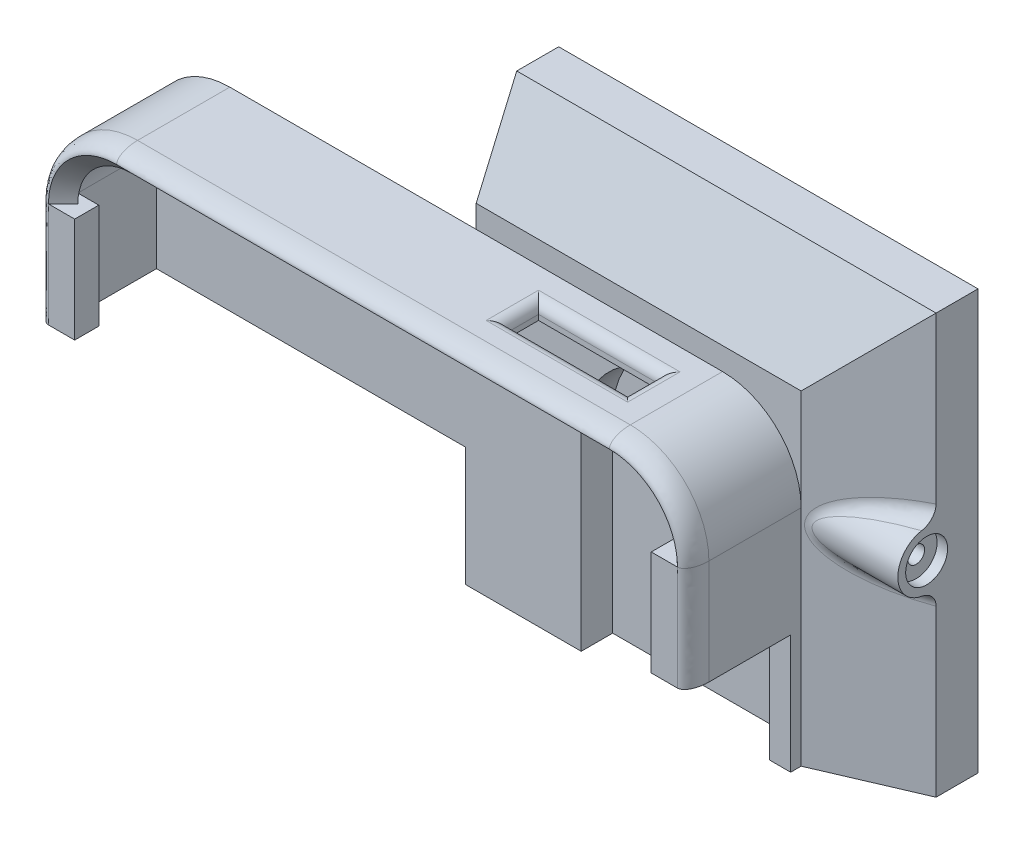
SolidWorks part; units mm, degrees
ref_plane "Front Plane" through (0, 0, 0) normal (0, 0, 1) x (1, 0, 0)
ref_plane "Top Plane" through (0, 0, 0) normal (0, 1, 0) x (1, 0, 0)
ref_plane "Right Plane" through (0, 0, 0) normal (1, 0, 0) x (0, 0, -1)
sketch "Sketch1" plane through (0, 0, 0) normal (0, 0, 1) x (1, 0, 0)
  line L0 (31, 17.5) -> (31, 0)
  line L1 (0, 0) -> (62, 0)
  line L2 (0, 0) -> (0, 10)
  line L3 (7.5, 17.5) -> (54.5, 17.5)
  line L4 (62, 0) -> (62, 10)
  line L5 (7.5, 16) -> (54.5, 16)
  line L9 (1.5, 0) -> (1.5, 10)
  line L12 (60.5, 10) -> (60.5, 0)
  arc A0 (0, 10) -> (7.5, 17.5) centre (7.5, 10) cw
  arc A1 (62, 10) -> (54.5, 17.5) centre (54.5, 10) ccw
  arc A2 (1.5, 10) -> (7.5, 16) centre (7.5, 10) cw
  arc A3 (60.5, 10) -> (54.5, 16) centre (54.5, 10) ccw
  dimension "D5" = 1.5
extrude "Boss-Extrude1" add sketch "Sketch1" along normal blind 10.8 contours L9 A2 L5 L0 L3 A0 L2 L1 | A3 L12 L1 L4 A1 L3 L0 L5 region at (42.75, 17.144, 0) region at (30.644, 16.75, 0)
sketch "Sketch2" plane through (0, 0, 0) normal (0, 0, -1) x (-1, 0, 0)
  line L0 (-1.5, 0) -> (-1.5, 10)
  line L1 (-7.5, 16) -> (-54.5, 16)
  line L2 (-60.5, 0) -> (-60.5, 10)
  line L3 (-60.5, 0) -> (-1.5, 0)
  arc A0 (-1.5, 10) -> (-7.5, 16) centre (-7.5, 10) ccw
  arc A1 (-54.5, 16) -> (-60.5, 10) centre (-54.5, 10) ccw
extrude "Boss-Extrude2" add sketch "Sketch2" against normal blind 1 separate body
combine bodies "Combine1" operation type add bodies to combine 102 101
sketch "Sketch3" plane through (0, 0, 10.8) normal (0, 0, 1) x (1, 0, 0)
  line L0 (0, 0) -> (3.5, 0)
  line L1 (0, 0) -> (0, 10)
  line L2 (0, 0) -> (0, 10) construction
  line L3 (3.5, 0) -> (3.5, 10)
  line L4 (3.5, 10) -> (0, 10)
  line L5 (1.5, 10) -> (1.5, 0)
  line L6 (31, 16) -> (31, -7.5027)
  line L7 (7.5, 16) -> (54.5, 16) construction
  line L8 (60.5, 10) -> (60.5, 0)
  line L9 (62, 0) -> (58.5, 0)
  line L10 (58.5, 10) -> (62, 10)
  line L11 (58.5, 0) -> (58.5, 10)
  line M7 (1.5, 0) -> (1.5, 10)
  line M11 (60.5, 10) -> (60.5, 0)
  dimension "D1" = 3.5
  dimension "D2" = 10
extrude "Boss-Extrude3" add sketch "Sketch3" against normal blind 2.3 contours L3 L4 L0 M7 | L11 L9 L10 M11 region at (2.5, 5, 10.8) region at (59.5, 5, 10.8)
fillet "Fillet1" radius 1 5 edges at (0, 5, 10.8) (62, 5, 10.8) (2.1967, 15.3033, 10.8) (59.8033, 15.3033, 10.8) (31, 17.5, 10.8) second distance 2 first distance on face at (31, 9.4708, 10.8)
sketch "Sketch4" plane through (0, 17.5, 0) normal (0, 1, 0) x (1, 0, 0)
  line L0 (62, -8.8) -> (62, 0) construction
  line L1 (51.5, -6.05) -> (40, -6.05)
  line L2 (51.5, -6.05) -> (51.5, -3.05)
  line L3 (51.5, -3.05) -> (40, -3.05)
  line L4 (40, -6.05) -> (40, -3.05)
  line L5 (7.5, 0) -> (54.5, 0) construction
  dimension "D1" = 10.5
  dimension "D2" = 11.5
  dimension "D3" = 3.05
  dimension "D4" = 3
extrude "Cut-Extrude1" cut sketch "Sketch4" against normal up to next
sketch "Sketch5" plane through (0, 0, 10.8) normal (0, 0, 1) x (1, 0, 0)
  line L1 (7.5, 15) -> (54.5, 15)
  line L2 (7.5, 16) -> (54.5, 16) construction
  line L4 (3.5, 10) -> (1.5, 10) construction
  line L5 (31, 16.5) -> (31, -2.3238) construction
  line L6 (54.5, 16.5) -> (7.5, 16.5) construction
  line L7 (59.5, 10) -> (60.5, 10)
  line L8 (54.5, 16) -> (7.5, 16)
  line L9 (1.5, 10) -> (2.5, 10)
  arc A1 (2.5, 10) -> (7.5, 15) centre (7.5, 10) cw
  arc A2 (59.5, 10) -> (54.5, 15) centre (54.5, 10) ccw
  arc A3 (60.5, 10) -> (54.5, 16) centre (54.5, 10) ccw
  arc A4 (7.5, 16) -> (1.5, 10) centre (7.5, 10) ccw
  dimension "D1" = 1
extrude "Boss-Extrude4" add sketch "Sketch5" against normal blind 2.3
chamfer "Chamfer1" distance 1.5 angle 45 3 edges at (58.0355, 13.5355, 10.8) (31, 15, 10.8) (3.9645, 13.5355, 10.8)
chamfer "Chamfer3" distance 1 angle 45 3 edges at (58.0355, 13.5355, 8.5) (31, 15, 8.5) (3.9645, 13.5355, 8.5)
sketch "Sketch6" plane through (0, 0, 0) normal (0, 0, -1) x (-1, 0, 0)
  line L0 (-59.98, 0) -> (-59.98, 6.7)
  line L1 (-59.98, 0) -> (-42.02, 0)
  line L2 (-42.02, 0) -> (-42.02, 6.7)
  arc A0 (-42.02, 6.7) -> (-59.98, 6.7) centre (-51, 6.7) ccw
extrude "Cut-Extrude2" cut sketch "Sketch6" against normal blind 2
sketch "Sketch9" plane through (0, 0, 0) normal (0, 0, -1) x (-1, 0, 0)
  line L0 (-62, 10) -> (-62, 0)
  line L1 (-62, 0) -> (-59.98, 0)
  line L2 (-59.98, 0) -> (-59.98, 6.7)
  line L3 (-42.02, 6.7) -> (-42.02, 0)
  line L4 (-42.02, 0) -> (-40, 0)
  line L5 (-42.02, 0) -> (0, 0) construction
  line L6 (-40, 0) -> (-40, 10)
  line L8 (-54.5, 17.5) -> (-47.5, 17.5)
  arc A0 (-59.98, 6.7) -> (-42.02, 6.7) centre (-51, 6.7) cw
  arc A1 (-47.5, 17.5) -> (-40, 10) centre (-47.5, 10) cw
  arc A2 (-54.5, 17.5) -> (-62, 10) centre (-54.5, 10) ccw
extrude "Boss-Extrude6" add sketch "Sketch9" along normal blind 2
fillet "Fillet2" radius 1 4 edges at (45.75, 17.5, 3.05) (51.5, 17.5, 4.55) (45.75, 17.5, 6.05) (40, 17.5, 4.55)
sketch "Sketch10" plane through (0, 0, -2) normal (0, 0, -1) x (-1, 0, 0)
  line L0 (-62, 10) -> (-62, 0)
  line L1 (-62, 0) -> (-40, 0)
  line L2 (-40, 0) -> (-40, 10)
  line L3 (-54.5, 17.5) -> (-47.5, 17.5)
  arc A0 (-62, 10) -> (-54.5, 17.5) centre (-54.5, 10) cw
  arc A1 (-40, 10) -> (-47.5, 17.5) centre (-47.5, 10) ccw
extrude "Boss-Extrude7" add sketch "Sketch10" along normal blind 1.87
sketch "Sketch11" plane through (0, 0, -2) normal (0, 0, 1) x (1, 0, 0)
  circle A0 centre (51, 8.65) radius 2.5
  dimension "D1" = 5
extrude "Cut-Extrude3" cut sketch "Sketch11" against normal through all
sketch "Sketch20" plane through (0, 0, -3.87) normal (0, 0, -1) x (-1, 0, 0)
  line L0 (-51, 28.65) -> (-51, -11.35) construction
  line L1 (-71, 28.65) -> (-31, 28.65)
  line L2 (-71, 28.65) -> (-71, -11.35)
  line L3 (-71, -11.35) -> (-31, -11.35)
  line L4 (-31, 28.65) -> (-31, -11.35)
  line L5 (-71, 8.65) -> (-31, 8.65) construction
  line L7 (-68.6, 26.25) -> (-33.4, 26.25)
  line L8 (-68.6, 26.25) -> (-68.6, -8.95)
  line L9 (-68.6, -8.95) -> (-33.4, -8.95)
  line L10 (-33.4, 26.25) -> (-33.4, -8.95)
  circle A0 centre (-51, 8.65) radius 2.5 construction
  dimension "D1" = 40
  dimension "D2" = 40
  dimension "D3" = 0
  dimension "D4" = 0
  dimension "D5" = 35.2
  dimension "D6" = 35.2
  dimension "D7" = 17.6
  dimension "D8" = 17.6
extrude "Boss-Extrude8" add sketch "Sketch20" along normal blind 4 separate body
sketch "Sketch21" plane through (0, 0, 0) normal (0, -1, 0) x (1, 0, 0)
  line L0 (62, -3.87) -> (71, -3.87)
  line L1 (71, -3.87) -> (62, 0)
  line L2 (62, 8.8) -> (62, -3.87) construction
  line L3 (62, 0) -> (62, -3.87)
  dimension "D1" = 9
extrude "Boss-Extrude9" add sketch "Sketch21" along normal up to surface and the other way up to surface up to face at (51, -11.35, -5.87) other way up to face at (51, 28.65, -5.87)
sketch "Sketch28" plane through (0, 0, 0) normal (0, 0, -1) x (-1, 0, 0)
  line L0 (-31, 17.5) -> (-31, 0)
  line L1 (-31, -11.35) -> (-31, 28.65) construction
  line L4 (-40, 10) -> (-40, 0)
  line L5 (-40, 0) -> (0, 0)
  line L6 (0, 0) -> (0, 10)
  line L7 (-7.5, 17.5) -> (-47.5, 17.5)
  line L8 (-40, 10) -> (-40, 0)
  line L9 (-40, 0) -> (0, 0)
  line L10 (0, 0) -> (0, 10)
  line L11 (-7.5, 17.5) -> (-47.5, 17.5)
  arc A2 (-40, 10) -> (-47.5, 17.5) centre (-47.5, 10) ccw
  arc A3 (0, 10) -> (-7.5, 17.5) centre (-7.5, 10) ccw
  arc A4 (-40, 10) -> (-47.5, 17.5) centre (-47.5, 10) ccw
  arc A5 (0, 10) -> (-7.5, 17.5) centre (-7.5, 10) ccw
  arc M7 (-47.5, 17.5) -> (-40, 10) centre (-47.5, 10) cw
  line M8 (-40, 10) -> (-40, 0)
  line M9 (-40, 0) -> (0, 0)
  line M12 (-7.5, 17.5) -> (-47.5, 17.5)
  dimension "D1" = 0
extrude "Boss-Extrude22" add sketch "Sketch28" along normal up to surface (3.87 mm away) contours L0 M12 M7 M8 M9 region at (35.9396, 9.2536, 0) up to face at (53.5, 8.65, -3.87)
sketch "Sketch29" plane through (31, 0, 0) normal (-1, 0, 0) x (0, 0, 1)
  line L0 (-3.87, 28.65) -> (-3.87, 19.65)
  line L1 (-3.87, 17.5) -> (-3.87, 28.65) construction
  line L2 (-3.87, 19.65) -> (0, 19.65)
  line L3 (0, 19.65) -> (-3.87, 28.65)
  line L4 (-3.87, 28.65) -> (-3.8304, 28.713)
  line M6 (-3.87, 17.5) -> (-3.87, 28.65)
  dimension "D1" = 9
extrude "Boss-Extrude23" add sketch "Sketch29" against normal up to surface (40 mm away) contours L2 L3 M6 region at (31, 22.65, -2.58) up to face at (71, 8.65, -5.87)
sketch "Sketch30" plane through (0, 19.65, 0) normal (0, -1, 0) x (1, 0, 0)
  line L3 (62, 0) -> (71, -3.87)
  line L4 (71, -3.87) -> (71, 0)
  line L5 (71, 0) -> (62, 0)
  line L6 (62, 0) -> (71, -3.87)
  line L7 (71, -3.87) -> (71, 0)
  line L8 (71, 0) -> (62, 0)
  dimension "D1" = 0
extrude "Cut-Extrude8" cut sketch "Sketch30" against normal up to next
sketch "Sketch31" plane through (62, 0, 0) normal (-1, 0, 0) x (0, 0, 1)
  line L3 (0, 28.65) -> (-3.87, 28.65)
  line L4 (-3.87, 28.65) -> (0, 19.65)
  line L5 (0, 19.65) -> (0, 28.65)
  line L6 (0, 28.65) -> (-3.87, 28.65)
  line L7 (-3.87, 28.65) -> (0, 19.65)
  line L8 (0, 19.65) -> (0, 28.65)
  dimension "D1" = 0
extrude "Cut-Extrude9" cut sketch "Sketch31" against normal up to next
sketch "Sketch32" plane through (0, 19.65, 0) normal (0, -1, 0) x (1, 0, 0)
  line L5 (62, -3.87) -> (62, 0)
  line L6 (62, 0) -> (31, 0)
  line L7 (31, 0) -> (31, -3.87)
  line L8 (31, -3.87) -> (33.4, -3.87)
  line L9 (33.4, -3.87) -> (62, -3.87)
  line L10 (62, -3.87) -> (62, 0)
  line L11 (62, 0) -> (31, 0)
  line L12 (31, 0) -> (31, -3.87)
  line L13 (31, -3.87) -> (33.4, -3.87)
  line L14 (33.4, -3.87) -> (62, -3.87)
  dimension "D1" = 0
extrude "Boss-Extrude24" add sketch "Sketch32" along normal up to surface (2.15 mm away) up to face at (45.75, 17.5, 4.55)
sketch "Sketch33" plane through (0, 0, -3.87) normal (0, 0, -1) x (-1, 0, 0)
  line L0 (-54.5, 17.5) -> (-62, 17.5)
  line L1 (-62, 17.5) -> (-62, 10)
  arc A0 (-62, 10) -> (-54.5, 17.5) centre (-54.5, 10) cw
extrude "Boss-Extrude25" add sketch "Sketch33" against normal up to surface (3.87 mm away) up to face at (48.1, 18.36, 0)
sketch "Sketch34" plane through (0, 0, 0) normal (0, -1, 0) x (1, 0, 0)
  line L0 (60.5, 1) -> (62, 1)
  line L1 (31, 0) -> (31, 1)
  line L20 (0, 0) -> (31, 0)
  line L21 (31, 0) -> (31, -3.87)
  line L22 (31, -3.87) -> (33.4, -3.87)
  line L23 (33.4, -3.87) -> (62, -3.87)
  line L24 (62, -3.87) -> (62, 0)
  line L25 (62, 0) -> (62, 8.8)
  line L26 (61, 10.8) -> (58.5, 10.8)
  line L27 (58.5, 10.8) -> (58.5, 8.5)
  line L28 (58.5, 8.5) -> (60.5, 8.5)
  line L29 (60.5, 8.5) -> (60.5, 1)
  line L30 (60.5, 1) -> (59.98, 1)
  line L31 (59.98, 1) -> (59.98, -2)
  line L32 (59.98, -2) -> (42.02, -2)
  line L33 (42.02, -2) -> (42.02, 1)
  line L34 (42.02, 1) -> (1.5, 1)
  line L35 (1.5, 1) -> (1.5, 8.5)
  line L36 (1.5, 8.5) -> (3.5, 8.5)
  line L37 (3.5, 8.5) -> (3.5, 10.8)
  line L38 (3.5, 10.8) -> (1, 10.8)
  line L39 (0, 8.8) -> (0, 0)
  line L40 (0, 0) -> (31, 0)
  line L41 (31, 0) -> (31, -3.87)
  line L42 (31, -3.87) -> (33.4, -3.87)
  line L43 (33.4, -3.87) -> (62, -3.87)
  line L44 (62, -3.87) -> (62, 0)
  line L45 (62, 0) -> (62, 8.8)
  line L46 (61, 10.8) -> (58.5, 10.8)
  line L47 (58.5, 10.8) -> (58.5, 8.5)
  line L48 (58.5, 8.5) -> (60.5, 8.5)
  line L49 (60.5, 8.5) -> (60.5, 1)
  line L50 (60.5, 1) -> (59.98, 1)
  line L51 (59.98, 1) -> (59.98, -2)
  line L52 (59.98, -2) -> (42.02, -2)
  line L53 (42.02, -2) -> (42.02, 1)
  line L54 (42.02, 1) -> (1.5, 1)
  line L55 (1.5, 1) -> (1.5, 8.5)
  line L56 (1.5, 8.5) -> (3.5, 8.5)
  line L57 (3.5, 8.5) -> (3.5, 10.8)
  line L58 (3.5, 10.8) -> (1, 10.8)
  line L59 (0, 8.8) -> (0, 0)
  spline S2 degree 2 poles (-3722.018, -1283.947) (75.1864, -74.9368) (61.954, 9.3993) (61.9047, 9.714) (61.807, 9.9811) (61.6887, 10.3047) (61.5165, 10.5125) (61.4097, 10.6416) (61.2894, 10.7144) (30.6702, 29.2588) (-318.8135, -3970.7049) knots -71.74099 -71.74099 -71.74099 0.25 0.25 0.5 0.5 0.75 0.75 0.875 0.875 27.96208 27.96208 27.96208 only from (62, 8.8) to (61, 10.8)
  spline S3 degree 2 poles (335.3153, -3974.9417) (31.4549, 29.2365) (0.7111, 10.7147) (0.592, 10.643) (0.4846, 10.5139) (0.3135, 10.3082) (0.1946, 9.9856) (0.0962, 9.7183) (0.0462, 9.4006) (-13.1634, -74.4343) (3754.3791, -1367.695) knots -27.023504 -27.023504 -27.023504 0.125 0.125 0.25 0.25 0.5 0.5 0.75 0.75 72.303108 72.303108 72.303108 only from (1, 10.8) to (0, 8.8)
  spline S4 degree 2 poles (62, 8.8) (62, 9.1064) (61.954, 9.3993) (61.9047, 9.714) (61.807, 9.9811) (61.6887, 10.3047) (61.5165, 10.5125) (61.4097, 10.6416) (61.2894, 10.7144) (61.1481, 10.8) (61, 10.8) knots 0 0 0 0.25 0.25 0.5 0.5 0.75 0.75 0.875 0.875 1 1 1
  spline S5 degree 2 poles (1, 10.8) (0.8527, 10.8) (0.7111, 10.7147) (0.592, 10.643) (0.4846, 10.5139) (0.3135, 10.3082) (0.1946, 9.9856) (0.0962, 9.7183) (0.0462, 9.4006) (0, 9.1077) (0, 8.8) knots 0 0 0 0.125 0.125 0.25 0.25 0.5 0.5 0.75 0.75 1 1 1
  line M24 (31, 0) -> (31, -3.87)
  line M25 (31, -3.87) -> (33.4, -3.87)
  line M26 (33.4, -3.87) -> (62, -3.87)
  line M27 (62, -3.87) -> (62, 0)
  line M28 (62, 0) -> (62, 8.8)
  line M34 (60.5, 1) -> (59.98, 1)
  line M35 (59.98, 1) -> (59.98, -2)
  line M36 (59.98, -2) -> (42.02, -2)
  line M37 (42.02, -2) -> (42.02, 1)
  line M38 (42.02, 1) -> (1.5, 1)
  dimension "D1" = 0
extrude "Boss-Extrude26" add sketch "Sketch34" along normal up to surface (11.35 mm away) contours L1 L0 M24 M25 M26 M27 M28 M34 M35 M36 M37 M38 region at (58.1075, 0, -2.3535) region at (39.3369, 0, -1.8217) up to face at (57.25, -11.35, -4.8808)
sketch "Sketch37" plane through (71, 0, 0) normal (1, 0, 0) x (0, 0, -1)
  line L1 (3.87, -11.35) -> (3.87, 28.65) construction
  circle A0 centre (2.97, 8.65) radius 0.8065
  dimension "D2" = 1.613
  dimension "D3" = 0.9
  dimension "D1" = 17.6
extrude "Cut-Extrude13" cut sketch "Sketch37" against normal up to surface (17.5 mm away) up to face at (53.5, 8.65, -2)
sketch "Sketch38" plane through (71, 0, 0) normal (1, 0, 0) x (0, 0, -1)
  line L0 (3.87, 11.2486) -> (3.87, 6.0514)
  line L1 (3.87, -11.35) -> (3.87, 28.65) construction
  circle A0 centre (2.97, 8.65) radius 2.75
  line M3 (3.87, 28.65) -> (3.87, -11.35)
  dimension "D1" = 5.5
extrude "Boss-Extrude27" add sketch "Sketch38" against normal up to surface (9 mm away) contours A0 M3 region at (71, 8.65, -2.2712) up to face at (62, 0.3833, 4.65)
sketch "Sketch39" plane through (71, 0, 0) normal (1, 0, 0) x (0, 0, -1)
  circle A0 centre (2.97, 8.65) radius 2
  dimension "D1" = 4
extrude "Cut-Extrude15" cut sketch "Sketch39" against normal blind 1
sketch "Sketch40" plane through (70, 0, 0) normal (1, 0, 0) x (0, 0, -1)
  circle A0 centre (2.97, 8.65) radius 0.8065
  dimension "D1" = 1.613
extrude "Cut-Extrude16" cut sketch "Sketch40" against normal up to surface (21.5 mm away) up to face at (53.4961, 8.79, -2.1757)
fillet "Fillet3" radius 1.5 1 edges at (62.5116, 8.65, -0.22)
